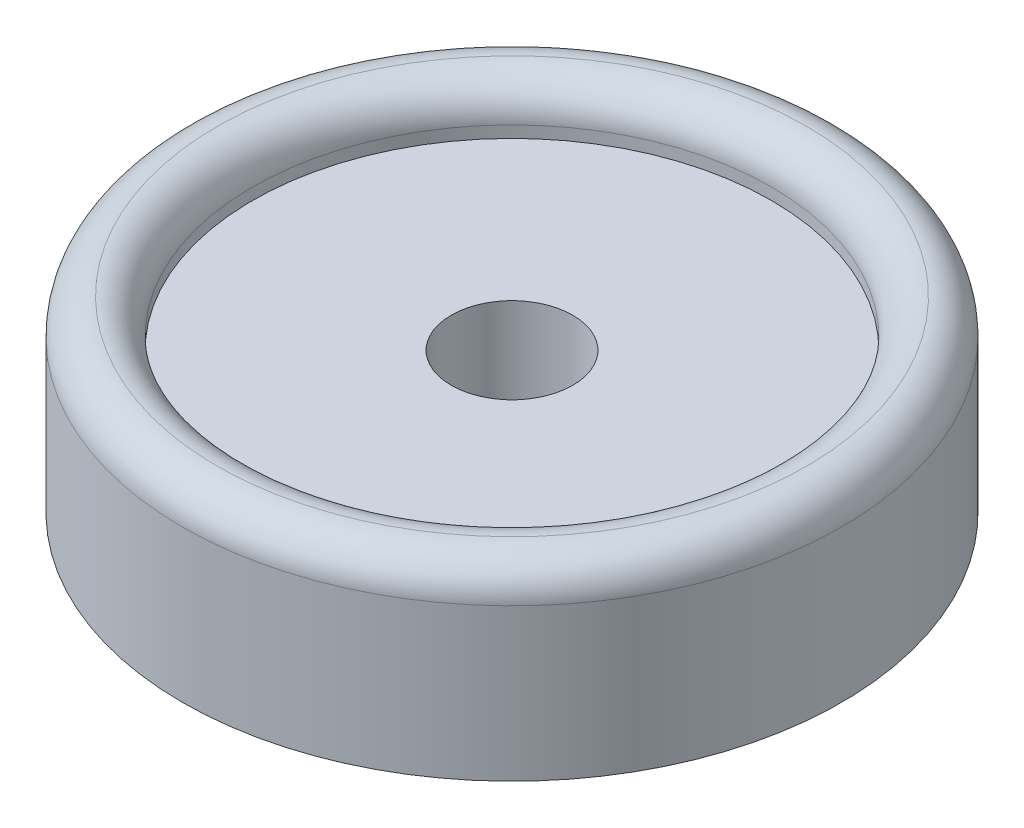
SolidWorks part; units mm, degrees
ref_plane "Front Plane" through (0, 0, 0) normal (0, 0, 1) x (1, 0, 0)
ref_plane "Top Plane" through (0, 0, 0) normal (0, 1, 0) x (1, 0, 0)
ref_plane "Right Plane" through (0, 0, 0) normal (1, 0, 0) x (0, 0, -1)
sketch "Sketch1" plane through (0, 0, 0) normal (0, 1, 0) x (1, 0, 0)
  circle A0 centre (0, 0) radius 8.1
  circle A1 centre (0, 0) radius 11.1
  dimension "D1" = 3
  dimension "D2" = 16.2
extrude "Boss-Extrude1" add sketch "Sketch1" along normal mid plane 100
sketch "Sketch2" plane through (0, -50, 0) normal (0, -1, 0) x (1, 0, 0)
  circle A0 centre (0, 0) radius 11.1
sketch "Sketch3" plane through (0, 0, 0) normal (0, 0, 1) x (1, 0, 0)
  line L1 (-101.5851, -102.8012) -> (101.5851, -102.8012)
  line L2 (-101.5851, -102.8012) -> (-101.5851, 102.8012)
  line L3 (-101.5851, 102.8012) -> (101.5851, 102.8012)
  line L4 (101.5851, -102.8012) -> (101.5851, 102.8012)
  line L5 (-101.5851, -102.8012) -> (101.5851, 102.8012) construction
  line L6 (-101.5851, 102.8012) -> (101.5851, -102.8012) construction
  point P0 (0, 0)
extrude "Cut-Extrude1" cut sketch "Sketch3" along normal through all
sketch "Sketch4" plane through (0, -50, 0) normal (0, -1, 0) x (1, 0, 0)
  circle A0 centre (0, 0) radius 11.1
extrude "Boss-Extrude3" add sketch "Sketch4" along normal mid plane 6
sketch "Sketch5" plane through (0, -47, 0) normal (0, 1, 0) x (1, 0, 0)
  circle A0 centre (0, 0) radius 2.6
  dimension "D1" = 5.2
extrude "Cut-Extrude2" cut sketch "Sketch5" against normal through all both and the other way through all
ref_plane "Plane2" through (0, 0, -6) normal (0, 0, 1) x (1, 0, 0)
sketch "Sketch6" plane through (0, 0, -6) normal (0, 0, 1) x (1, 0, 0)
  line L0 (0, 17.3633) -> (0, 69.1455) construction
  line L1 (11.1, 50) -> (8.1, 50) construction
  line L2 (7.6, 40) -> (22.6, 40)
  line L3 (7.6, 40) -> (7.6, 10)
  line L4 (7.6, 10) -> (22.6, 10)
  line L5 (22.6, 40) -> (22.6, 10)
  line L7 (-22.6, 40) -> (-22.6, 10)
  line L8 (-7.6, 10) -> (-22.6, 10)
  line L9 (-7.6, 40) -> (-7.6, 10)
  line L10 (-7.6, 40) -> (-22.6, 40)
  dimension "D1" = 10
  dimension "D2" = 30
  dimension "D3" = 7.6
  dimension "D4" = 15
extrude "Boss-Extrude4" add sketch "Sketch6" along normal mid plane 3
sketch "Sketch7" plane through (0, 0, -4.5) normal (0, 0, 1) x (1, 0, 0)
  line L1 (-54.6338, -47) -> (60.6792, -47)
  line L2 (-54.6338, -47) -> (-54.6338, 57.7454)
  line L3 (-54.6338, 57.7454) -> (60.6792, 57.7454)
  line L4 (60.6792, -47) -> (60.6792, 57.7454)
extrude "Cut-Extrude3" cut sketch "Sketch7" against normal through all both and the other way through all
sketch "Sketch8" plane through (0, -53, 0) normal (0, -1, 0) x (1, 0, 0)
  circle A0 centre (0, 0) radius 14.1
  circle A1 centre (0, 0) radius 11.1 construction
  circle A2 centre (0, 0) radius 11.1
  dimension "D1" = 3
extrude "Boss-Extrude5" add sketch "Sketch8" against normal blind 8
fillet "Fillet3" radius 1.5 2 edges at (0, -45, -14.1) (0, -45, -11.1)
